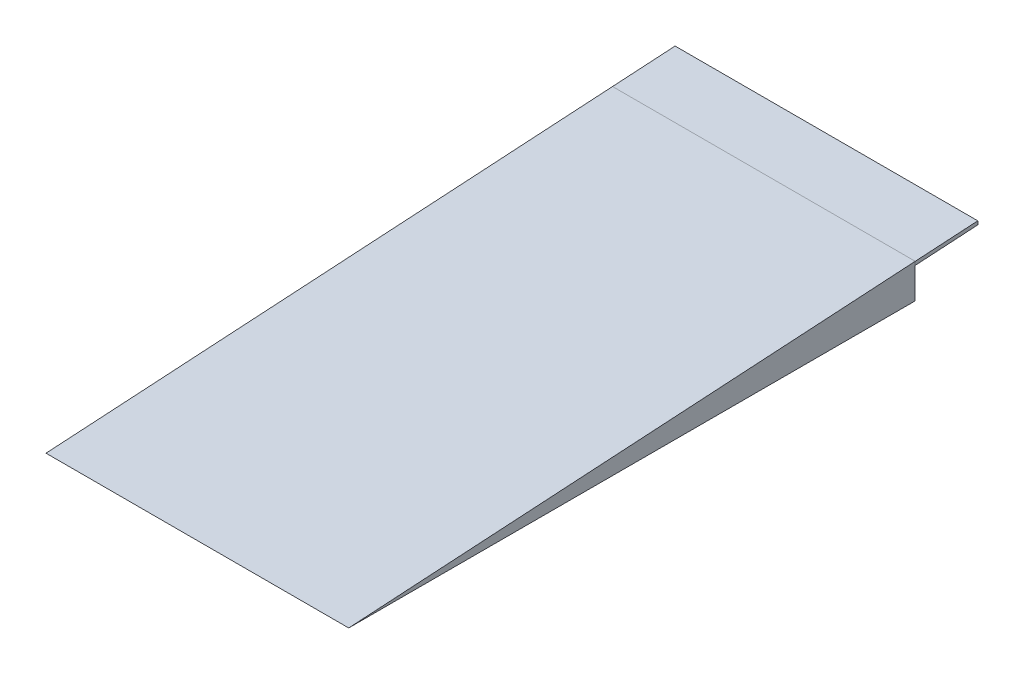
SolidWorks part; units mm, degrees
material "Pine"
ref_plane "Front" through (0, 0, 0) normal (0, 0, 1) x (1, 0, 0)
ref_plane "Top" through (0, 0, 0) normal (0, 1, 0) x (1, 0, 0)
ref_plane "Right" through (0, 0, 0) normal (1, 0, 0) x (0, 0, -1)
sketch "Sketch1" plane through (0, 0, 0) normal (1, 0, 0) x (0, 0, -1)
  line L0 (0, 0) -> (3042.432, 184.15)
  line L1 (3042.432, 184.15) -> (3042.432, 0)
  line L2 (3042.432, 0) -> (0, 0)
  dimension "D1" = 184.15
  dimension "D2" = 3048
extrude "Boss-Extrude1" add sketch "Sketch1" along normal mid plane 1625.6
shell "Shell1" thickness 19.05 removed face at (0, 92.075, -3042.432) removed face at (0, 0, -1521.216)
sketch "Sketch2" plane through (0, 0, 0) normal (1, 0, 0) x (0, 0, -1)
  line L3 (315.3103, 0) -> (3042.432, 0)
  line L4 (3042.432, 165.0651) -> (315.3103, 0)
  line L5 (3042.432, 0) -> (3042.432, 165.0651)
  line L6 (315.3103, 0) -> (3042.432, 0)
  line L7 (3042.432, 165.0651) -> (315.3103, 0)
  line L8 (3042.432, 0) -> (3042.432, 165.0651)
  dimension "D1" = 0
extrude "Boss-Extrude2" add sketch "Sketch2" along normal mid plane 19.05
sketch "Sketch3" plane through (0, 0, 0) normal (1, 0, 0) x (0, 0, -1)
  line L0 (3042.432, 184.15) -> (3378.3673, 204.4832)
  line L1 (3042.432, 184.15) -> (0, 0) construction
  line L2 (3378.3673, 204.4832) -> (3379.5182, 185.468)
  line L3 (3379.5182, 185.468) -> (3042.432, 165.0651)
  line L4 (3042.432, 0) -> (3042.432, 184.15) construction
  line L5 (3042.432, 184.15) -> (3042.432, 165.0651)
  dimension "D1" = 336.55
  dimension "D2" = 19.05
extrude "Boss-Extrude3" add sketch "Sketch3" along normal up to surface and the other way up to surface separate body up to face at (812.8, 61.3833, -2028.288) other way up to face at (-812.8, 61.3833, -2028.288)
